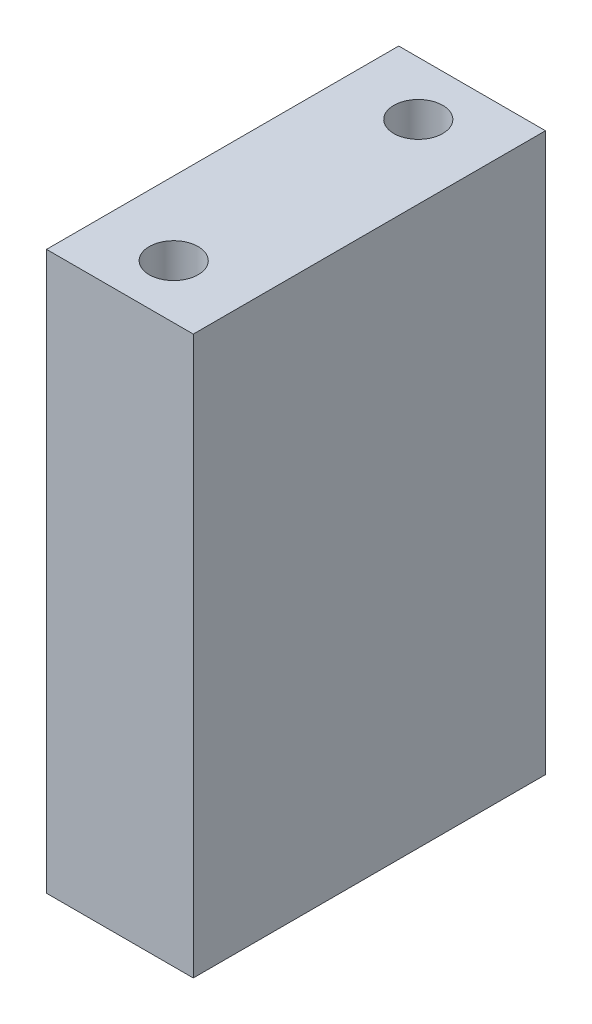
SolidWorks part; units mm, degrees
material "K110"
ref_plane "Front Plane" through (0, 0, 0) normal (0, 0, 1) x (1, 0, 0)
ref_plane "Top Plane" through (0, 0, 0) normal (0, 1, 0) x (1, 0, 0)
ref_plane "Right Plane" through (0, 0, 0) normal (1, 0, 0) x (0, 0, -1)
sketch "Sketch1" plane through (0, 0, 0) normal (0, 1, 0) x (1, 0, 0)
  line L1 (-7.5, 18) -> (7.5, 18)
  line L2 (-7.5, 18) -> (-7.5, -18)
  line L3 (-7.5, -18) -> (7.5, -18)
  line L4 (7.5, 18) -> (7.5, -18)
  line L5 (-7.5, 18) -> (7.5, -18) construction
  line L6 (-7.5, -18) -> (7.5, 18) construction
  point P0 (0, 0)
  dimension "D1" = 36
  dimension "D2" = 15
extrude "Boss-Extrude1" add sketch "Sketch1" against normal blind 57
hole_wizard "M6 Tapped Hole1" positions "Sketch5" profile "Sketch4" tap size "M6" standard "ISO"
sketch "Sketch5" plane through (0, 0, 0) normal (0, 1, 0) x (1, 0, 0)
  line L0 (7.5, 0) -> (-7.5, 0) construction
  line L1 (7.5, -18) -> (7.5, 18) construction
  line L2 (-7.5, 18) -> (-7.5, -18) construction
  point P1 (0, 12.5)
  point P3 (0, -12.5)
  dimension "D1" = 25
sketch "Sketch4" plane through (0, 0, -12.5) normal (1, 0, 0) x (0, 0, 1)
  line L0 (0, 0) -> (0, 16.5022)
  line L1 (0, 16.5022) -> (2.5, 15)
  line L2 (2.5, 15) -> (2.5, 0)
  line L5 (2.5, 0) -> (0, 0)
  line L10 (0, 16.5022) -> (-2.5, 15) construction
  line L11 (0, -6.35) -> (0, 107.95) construction
  dimension "Tap Drill Dia." = 5
  dimension "Tap Drill Depth" = 15
  dimension "Drill Angle" = 118
cosmetic thread "Hole Thread1"
cosmetic thread "Hole Thread2"
